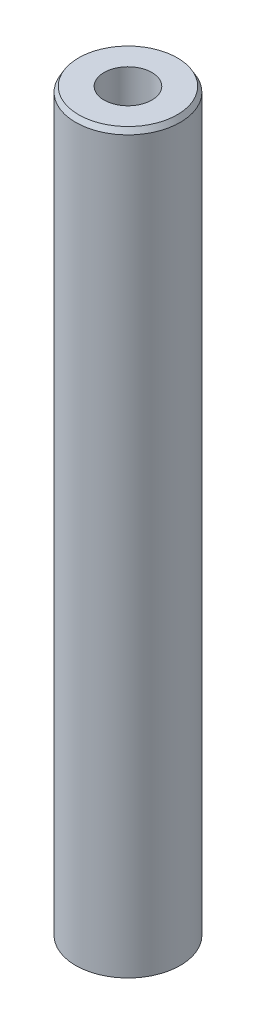
SolidWorks part; units mm, degrees
ref_plane "Front Plane" through (0, 0, 0) normal (0, 0, 1) x (1, 0, 0)
ref_plane "Top Plane" through (0, 0, 0) normal (0, 1, 0) x (1, 0, 0)
ref_plane "Right Plane" through (0, 0, 0) normal (1, 0, 0) x (0, 0, -1)
sketch "Sketch1" plane through (0, 0, 0) normal (0, 1, 0) x (1, 0, 0)
  circle A0 centre (0, 0) radius 42.5
  dimension "SHAFT_OD" = 85
extrude "Boss-Extrude1" add sketch "Sketch1" along normal blind 600
sketch "Sketch2" plane through (0, 0, 0) normal (0, 1, 0) x (1, 0, 0)
  circle A0 centre (0, 0) radius 19.4496
  dimension "BORE_D" = 38.8991
extrude "Cut-Extrude1" cut sketch "Sketch2" along normal through all
chamfer "Chamfer1" distance 4.169 angle 30 2 edges at (0, 600, 42.5) (0, 0, 42.5) first distance on face at (0, 600, 42.5) first distance on face at (0, 0, 19.4496)
